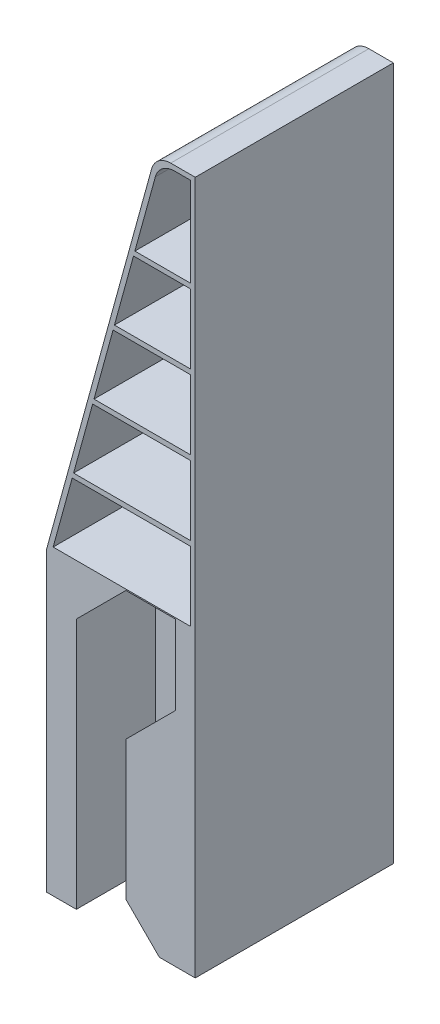
SolidWorks part; units mm, degrees
ref_plane "Front Plane" through (0, 0, 0) normal (0, 0, 1) x (1, 0, 0)
ref_plane "Top Plane" through (0, 0, 0) normal (0, 1, 0) x (1, 0, 0)
ref_plane "Right Plane" through (0, 0, 0) normal (1, 0, 0) x (0, 0, -1)
sketch "Sketch1" plane through (0, 0, 0) normal (0, 0, 1) x (1, 0, 0)
  line L0 (7.5, 15) -> (7.5, 55)
  line L1 (-7.5, -15) -> (7.5, -15)
  line L2 (-7.5, -15) -> (-7.5, 15)
  line L4 (7.5, -15) -> (7.5, 15)
  line L5 (-7.5, -15) -> (7.5, 15) construction
  line L6 (-7.5, 15) -> (7.5, -15) construction
  line L7 (7.5, 55) -> (5.0242, 55)
  line L8 (3.0958, 53.5303) -> (-7.5, 15)
  line L9 (-6.8439, 15.5) -> (-4.9189, 22.5)
  line L10 (5.4053, 54.5) -> (7, 54.5)
  line L11 (7, 54.5) -> (7, 45.5)
  line L12 (7, 15.5) -> (-6.8439, 15.5)
  line L13 (-4.9189, 22.5) -> (7, 22.5)
  line L15 (7, 23) -> (-4.7814, 23)
  line L16 (-4.7814, 23) -> (-2.8564, 30)
  line L17 (-2.8564, 30) -> (7, 30)
  line L19 (7, 30.5) -> (-2.7189, 30.5)
  line L20 (7, 37.5) -> (-0.7939, 37.5)
  line L21 (-0.6564, 38) -> (7, 38)
  line L22 (1.2686, 45) -> (7, 45)
  line L23 (7, 45.5) -> (1.4061, 45.5)
  line L24 (-7.5, 15) -> (7.5, 15) construction
  line L25 (1.4061, 45.5) -> (3.4769, 53.0303)
  line L26 (7, 45) -> (7, 38)
  line L27 (7, 37.5) -> (7, 30.5)
  line L28 (-0.6564, 38) -> (1.2686, 45)
  line L29 (-2.7189, 30.5) -> (-0.7939, 37.5)
  line L30 (7, 30) -> (7, 23)
  line L31 (7, 22.5) -> (7, 15.5)
  line L32 (-4.7814, 23) -> (-2.8564, 30)
  line L43 (3.3451, 33.4788) -> (3.3747, 33.4788) construction
  line L44 (2.1405, 30.5) -> (2.0718, 30) construction
  line L47 (1.0405, 22.5) -> (1.1093, 23) construction
  arc A16 (3.4769, 53.0303) -> (5.4053, 54.5) centre (5.4053, 52.5) cw
  arc A17 (5.0242, 55) -> (3.0958, 53.5303) centre (5.0242, 53) ccw
  point P0 (0, 0)
  point P10 (7, 22.5514)
  point P13 (7, 22.1785)
  point P14 (7.0492, 22.6785)
  point P15 (0, 0)
  point P16 (7, 22.1327)
  point P17 (7, 28.5)
  point P18 (0, 0)
  point P19 (7, 29)
  point P20 (7, 29.0606)
  point P21 (0, 0)
  point P22 (0, 0)
  point P23 (7, 37.9762)
  point P24 (7, 43.5988)
  point P25 (7, 43.5397)
  point P26 (7, 44.1117)
  point P27 (7.0436, 44.1117)
  point P28 (0.3831, 43.5988)
  point P31 (0.1648, 43.5988)
  point P32 (0.2144, 43.5977)
  point P33 (0.2896, 44.0977)
  point P34 (7, 38.0074)
  point P37 (7, 36)
  point P38 (7, 36.0433)
  point P39 (-1.0868, 38.5418)
  point P40 (-3.6098, 28.5)
  point P43 (-3.4842, 29)
  point P44 (-3.5279, 29.0017)
  point P45 (-3.5345, 28.4992)
  point P46 (-5.0023, 22.9294)
  point P47 (-4.984, 22.6926)
  point P49 (-4.7691, 22.6947)
  point P50 (-5.0614, 22.6947)
  point P51 (-5.1617, 22.144)
  point P55 (0.3561, 44.0969)
  point P56 (-1.4573, 36)
  point P72 (3.5, 55)
  point P73 (-1.7341, 36)
  point P74 (-1.6736, 36.0019)
  point P81 (0, 0)
  point P82 (0, 0)
  dimension "D25" = 2
  dimension "D1" = 30
  dimension "D2" = 15
  dimension "D3" = 40
  dimension "D4" = 4
  dimension "D5" = 0.5
  dimension "D6" = 0.5
  dimension "D7" = 0.5
  dimension "D8" = 0.5
  dimension "D9" = 0.5
  dimension "D10" = 7
  dimension "D11" = 0.5
  dimension "D12" = 0.5
  dimension "D13" = 7
  dimension "D14" = 7
  dimension "D15" = 0.5
  dimension "D16" = 7
extrude "Boss-Extrude1" add sketch "Sketch1" along normal blind 10 and the other way blind 10 contours L7 L8 L2 L1 L4 L0 L23 L25 L10 L11 L21 L28 L22 L26 L19 L29 L20 L27 L15 L16 L17 L30 L13 L31 L12 L9 region at (0.3064, 4.2035, 0)
sketch "Sketch2" plane through (0, 0, 10) normal (0, 0, 1) x (1, 0, 0)
  line L0 (5.5, 7.3787) -> (5.5, 15.3787)
  line L2 (5.5, 15.3787) -> (0.5, 15.3787)
  line L3 (0.5, 15.3787) -> (-4.5, 10.3787)
  line L4 (-4.5, 10.3787) -> (-4.5, -15.6213)
  line L6 (-4.5, -15.6213) -> (4.5, -15.6213)
  line L7 (4.5, -15.6213) -> (0.5, -11.6213)
  line L8 (0.5, -11.6213) -> (0.5, 2.3787)
  line L9 (0.5, 2.3787) -> (5.5, 7.3787)
  line L10 (0.5, 0) -> (-4.5, 0) construction
  dimension "D1" = 5
  dimension "D2" = 9
  dimension "D3" = 10
  dimension "D4" = 45
  dimension "D5" = 8
  dimension "D6" = 45
  dimension "D7" = 5
  dimension "D8" = 14
  dimension "D9" = 4.5
extrude "Cut-Extrude1" cut sketch "Sketch2" against normal blind 8
mirror "Mirror1" about plane through (0, 0, 0) normal (0, 0, 1) of "Cut-Extrude1"
sketch "Sketch4" plane through (0, 0, 0) normal (0, 0, 1) x (1, 0, 0)
  line L0 (5.5, 7.3787) -> (5.5, 15.3787) construction
  line L1 (5.5, 15.3787) -> (0.5, 15.3787) construction
  circle A0 centre (1.5, 9.3787) radius 1.75
  dimension "D1" = 3.5
  dimension "D2" = 4
  dimension "D3" = 6
extrude "Cut-Extrude2" cut sketch "Sketch4" against normal through all both and the other way through all
